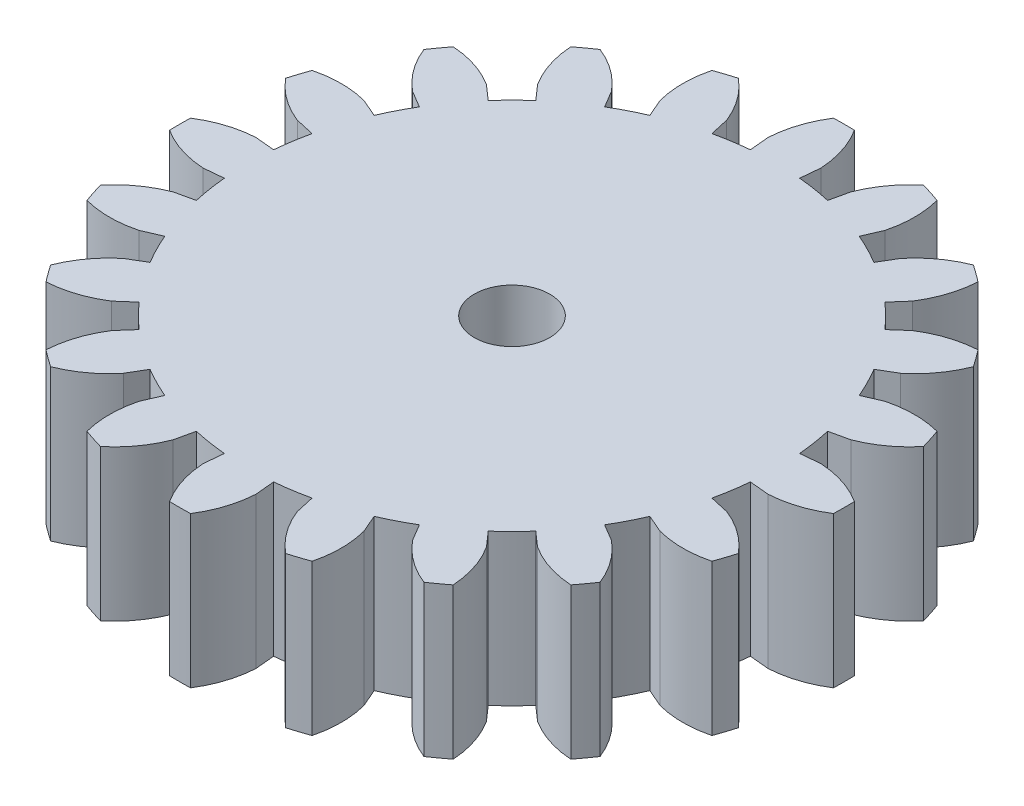
SolidWorks part; units mm, degrees
ref_plane "Спереди" through (0, 0, 0) normal (0, 0, 1) x (1, 0, 0)
ref_plane "Сверху" through (0, 0, 0) normal (0, 1, 0) x (1, 0, 0)
ref_plane "Справа" through (0, 0, 0) normal (1, 0, 0) x (0, 0, -1)
other "Configuration Table"
sketch "Эскиз1" plane through (0, 0, 0) normal (0, 1, 0) x (1, 0, 0)
  circle A0 centre (0, 0) radius 17.5
  dimension "D1" = 35
extrude "Бобышка-Вытянуть1" add sketch "Эскиз1" along normal blind 10
sketch "Эскиз2" plane through (0, 0, 0) normal (0, -1, 0) x (1, 0, 0)
  line L0 (0, 0) -> (0, 22) construction
  line L1 (0, 0) -> (-1.7523, 18.712) construction
  line L2 (0, 0) -> (1.7523, 18.712) construction
  line L5 (-1.5692, 19.9383) -> (0, 0) construction
  line L6 (0, 0) -> (1.5692, 19.9383) construction
  line L7 (-0.6949, 21.989) -> (0, 0) construction
  line L8 (-1.6317, 17.4238) -> (-1.7523, 18.712)
  line L9 (1.7523, 18.712) -> (1.6317, 17.4238)
  circle A0 centre (0, 0) radius 18.7938 construction
  circle A1 centre (0, 0) radius 20 construction
  circle A2 centre (0, 0) radius 22 construction
  arc A3 (-0.6949, 21.989) -> (0.6949, 21.989) centre (0, 0) cw
  arc A4 (-1.6317, 17.4238) -> (1.6317, 17.4238) centre (0, 0) cw
  circle A5 centre (0, 0) radius 17.5 construction
  arc A6 (-1.5692, 19.9383) -> (1.5692, 19.9383) centre (0, 0) cw construction
  arc A7 (-1.7523, 18.712) -> (-0.6949, 21.989) centre (5.0681, 18.3203) cw
  arc A8 (0.6949, 21.989) -> (1.7523, 18.712) centre (-5.0681, 18.3203) cw
  point P12 (0, 20)
  point P16 (0, 22)
  point P22 (0, 17.5)
  dimension "D1" = 37.5877
  dimension "D2" = 40
  dimension "D3" = 44
  dimension "D4" = 5.35
  dimension "D5" = 4.5
  dimension "D6" = 1.81
extrude "Бобышка-Вытянуть2" add sketch "Эскиз2" against normal blind 10
pattern_circular "Круговой массив1" count 20 over 360 about axis through (0, 10, 0) along (0, -1, 0) of "Бобышка-Вытянуть2" reverse direction yes
sketch "Эскиз3" plane through (0, 0, 0) normal (0, -1, 0) x (1, 0, 0)
  circle A0 centre (0, 0) radius 2.5
  dimension "D1" = 5
extrude "Вырез-Вытянуть1" cut sketch "Эскиз3" against normal through all
equation "\"Ширина груза\"= 160"
equation "\"Глубина груза\"= 240"
equation "\"Высота груза\"= 160"
equation "\"Ширина ячейки\"= \"Ширина груза\" + 10"
equation "\"Глубина ячейки\"= \"Глубина груза\" + 10"
equation "\"Высота ячейки\"= \"Высота груза\" + 10 + 13"
equation "\"Колво ячеек ширина\"= 2"
equation "\"Колво ячеек высота\"= 2"
equation "\"Толщина стенки\"= \"Толщина тонких панелей\""
equation "\"Крепление дверцы\"= 5 "
equation "\"Ширина рейки\"= \"Толщина шестерни\""
equation "\"Высота рейки\"= 20"
equation "\"Высота пола\"= 2*\"Толщина тонких панелей\""
equation "\"Колво полозьев\"= 5"
equation "\"Отступ рейки\"= 20"
equation "\"Глубина каретки\"= \"Глубина ячейки\" + 30 + \"Мотор Y высота корпуса\" + 20"
equation "\"Длинна рейки\"= (\"Ширина ячейки\"+\"Толщина вертикальных стенок\"+\"Крепление дверцы\")*\"Колво ячеек ширина\"+\"Ширина ячейки выгрузки\"*\"Колво выгрузки\"+\"Толщина вертикальных стенок\"+2*\"Отступ крепления мотора фиксации\"-\"Крепление дверцы\"*\"Колво ячеек ширина\""
equation "\"Отступ шпильки\"= 26"
equation "\"Диаметр шпильки\"= 5"
equation "\"Длинна шпильки\"= (\"Высота ячейки\"+\"Толщина горизонтальных плит\"+\"Высота пола\")*\"Колво ячеек высота\"+2*(\"Толщина горизонтальных плит\"+\"Отступ рейки\")"
equation "\"Ширина пластины\"= 50  "
equation "\"Высота зона выгрузки\"= \"Высота ячейки\" * 2 + \"Толщина стенки\" * 2"
equation "\"Колво выгрузки\"= 1"
equation "\"Ширина ячейки выгрузки\"= \"Ширина ячейки\"+\"Толщина вертикальных стенок\"+2*\"Отступ крепления мотора фиксации\""
equation "\"Отступ крепления мотора фиксации\"= (\"Ширина пластины\"+20-\"Толщина вертикальных стенок\")/2"
equation "\"Мотор X ширина корпуса\"= 42.3"
equation "\"Мотор X высота корпуса\"= 42.3"
equation "\"Мотор X длина корпуса\"= 40"
equation "\"Мотор X вылет вала\"= 19.8"
equation "\"Мотор Y ширина корпуса\"= 42.3"
equation "\"Мотор Y высота корпуса\"= 42.3"
equation "\"Мотор Y длина корпуса\"= 48"
equation "\"Мотор Y вылет вала\"= 30"
equation "\"Мотор Z ширина корпуса\"= 42"
equation "\"Мотор Z высота корпуса\"= 42"
equation "\"Мотор Z длина корпуса\"= 40"
equation "\"Мотор Z вылет вала\"= 23"
equation "\"Мотор диаметр вала ПРЕДВ\"= 5"
equation "\"Мотор шаг крепления ПРЕДВ\"= 31"
equation "\"Мотор диаметр отверстий ПРЕДВ\"= 3"
equation "\"Мотор глубина отверстий ПРЕДВ\"= 4.5"
equation "\"Мотор диаметр буртика ПРЕДВ\"= 22"
equation "\"Мотор высота буртика ПРЕДВ\"= 2"
equation "\"Мотор диаметр шкива ПРЕДВ\"= 16"
equation "\"Мотор длина шкива ПРЕДВ\"= 12"
equation "\"Мотор отступ шкива ПРЕДВ\"= 5"
equation "\"Мотор X шаг градусов\"= 1.8"
equation "\"Мотор Y шаг градусов\"= 1.8"
equation "\"Мотор Z шаг градусов\"= 1.8"
equation "\"Мотор Y диаметр ротора\"= 25.78"
equation "\"Толщина шестерни\"= 10"
equation "\"D1@Бобышка-Вытянуть1\"=\"Толщина шестерни\""
equation "\"D1@Бобышка-Вытянуть2\"=\"Толщина шестерни\""
equation "\"D1@Эскиз3\"=\"Мотор диаметр вала ПРЕДВ\""
equation "\"Толщина тонких панелей\"= 6"
equation "\"Толщина вертикальных стенок\"= 6"
equation "\"Толщина горизонтальных плит\"= 6"
equation "\"Базовая высота корпуса\"= (\"Высота ячейки\"+\"Толщина тонких панелей\"+\"Высота пола\")*\"Колво ячеек высота\"+6*\"Толщина тонких панелей\"+\"Мотор X ширина корпуса\"+\"Мотор Y ширина корпуса\"+75"
equation "\"Высота корпуса\"= (\"Высота ячейки\"+\"Толщина горизонтальных плит\"+\"Высота пола\")*\"Колво ячеек высота\"+2*\"Толщина горизонтальных плит\"+4*\"Толщина тонких панелей\"+\"Мотор X ширина корпуса\"+\"Мотор Y ширина корпуса\"+75"
equation "\"Смещение центра корпуса\"= (\"Высота корпуса\"-\"Базовая высота корпуса\")/2-(\"Толщина горизонтальных плит\"-\"Толщина тонких панелей\")"
equation "\"Отметка пола\"= -\"Базовая высота корпуса\"/2+\"Толщина тонких панелей\""
equation "\"Отметка потолка\"= \"Отметка пола\"+\"Высота корпуса\"-2*\"Толщина горизонтальных плит\""
equation "\"Отметка верхней полки\"= \"Отметка потолка\"-(28+\"Толщина тонких панелей\")-\"Высота ячейки\"-\"Высота пола\""
equation "\"Отметка нижней полки\"= \"Отметка верхней полки\"-\"Высота ячейки\"-\"Высота пола\"-\"Толщина горизонтальных плит\""
